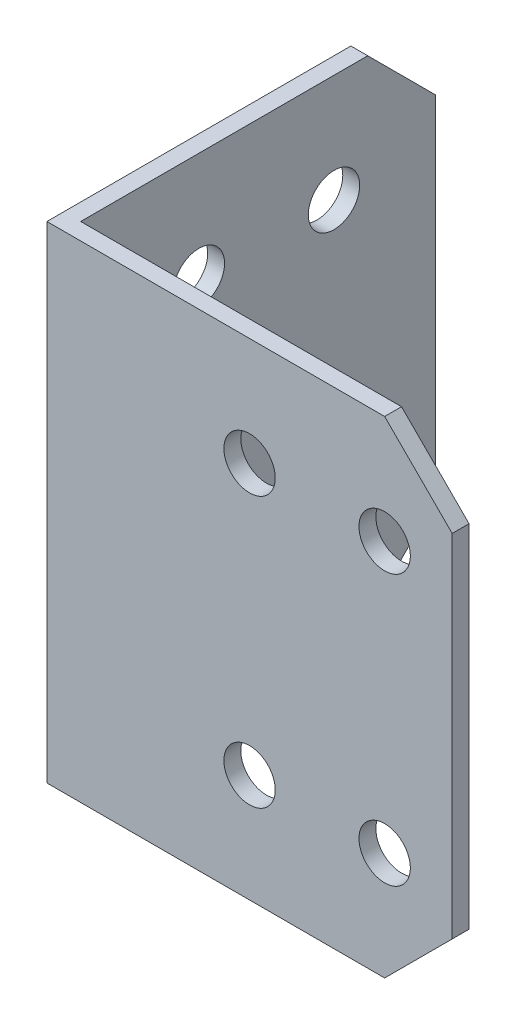
SolidWorks part; units mm, degrees
material "6061-T6 (SS)"
ref_plane "Front Plane" through (0, 0, 0) normal (0, 0, 1) x (1, 0, 0)
ref_plane "Top Plane" through (0, 0, 0) normal (0, 1, 0) x (1, 0, 0)
ref_plane "Right Plane" through (0, 0, 0) normal (1, 0, 0) x (0, 0, -1)
sketch "Sketch1" plane through (0, 0, 0) normal (0, 1, 0) x (1, 0, 0)
  line L1 (-18.1093, 28.5162) -> (-16.5218, 28.5162)
  line L2 (-18.1093, 28.5162) -> (-18.1093, -6.4088)
  line L4 (-16.5218, 28.5162) -> (-16.5218, -4.8213)
  line L5 (-18.1093, -6.4088) -> (19.9907, -6.4088)
  line L7 (-16.5218, -4.8213) -> (19.9907, -4.8213)
  line L8 (19.9907, -6.4088) -> (19.9907, -4.8213)
  dimension "D1" = 1.5875
  dimension "D2" = 1.5875
  dimension "D3" = 34.925
  dimension "D4" = 38.1
extrude "Boss-Extrude1" add sketch "Sketch1" along normal blind 45.72 contours L2 L5 L8 L7 L4 L1
sketch "Sketch2" plane through (0, 0, 4.8213) normal (0, 0, -1) x (-1, 0, 0)
  line L1 (-13.6407, 35.56) -> (-0.9407, 35.56) construction
  line L2 (-13.6407, 35.56) -> (-13.6407, 10.16) construction
  line L3 (-13.6407, 10.16) -> (-0.9407, 10.16) construction
  line L4 (-0.9407, 35.56) -> (-0.9407, 10.16) construction
  line L5 (18.1093, 45.72) -> (18.1093, 0) construction
  line L6 (16.5218, 45.72) -> (-19.9907, 45.72) construction
  circle A0 centre (-0.9407, 35.56) radius 2.413
  circle A1 centre (-13.6407, 35.56) radius 2.413
  circle A2 centre (-13.6407, 10.16) radius 2.413
  circle A3 centre (-0.9407, 10.16) radius 2.413
  dimension "D5" = 4.826
  dimension "D1" = 12.7
  dimension "D2" = 19.05
  dimension "D3" = 10.16
  dimension "D4" = 25.4
extrude "Cut-Extrude1" cut sketch "Sketch2" against normal through all
sketch "Sketch3" plane through (-16.5218, 0, 0) normal (1, 0, 0) x (0, 0, -1)
  line L0 (-6.4088, 45.72) -> (-6.4088, 0) construction
  line L1 (18.9912, 35.56) -> (6.2912, 35.56) construction
  line L2 (18.9912, 35.56) -> (18.9912, 10.16) construction
  line L3 (18.9912, 10.16) -> (6.2912, 10.16) construction
  line L4 (6.2912, 35.56) -> (6.2912, 10.16) construction
  line L5 (28.5162, 45.72) -> (-4.8213, 45.72) construction
  circle A0 centre (6.2912, 35.56) radius 2.413
  circle A1 centre (18.9912, 35.56) radius 2.413
  circle A2 centre (18.9912, 10.16) radius 2.413
  circle A3 centre (6.2912, 10.16) radius 2.413
  dimension "D5" = 4.826
  dimension "D1" = 12.7
  dimension "D2" = 25.4
  dimension "D3" = 10.16
  dimension "D4" = 12.7
extrude "Cut-Extrude2" cut sketch "Sketch3" against normal through all
chamfer "Chamfer1" distance 6.35 angle 45 4 edges at (19.9907, 45.72, 5.615) (19.9907, 0, 5.615) (-17.3155, 0, -28.5162) (-17.3155, 45.72, -28.5162)
